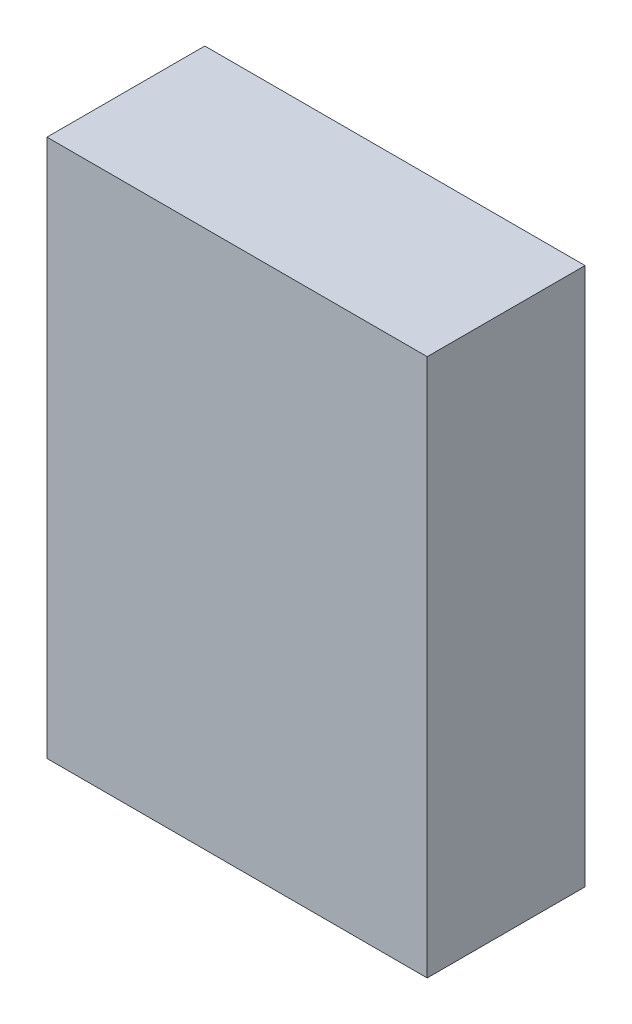
SolidWorks part; units mm, degrees
ref_plane "Front Plane" through (0, 0, 0) normal (0, 0, 1) x (1, 0, 0)
ref_plane "Top Plane" through (0, 0, 0) normal (0, 1, 0) x (1, 0, 0)
ref_plane "Right Plane" through (0, 0, 0) normal (1, 0, 0) x (0, 0, -1)
sketch "Sketch1" plane through (0, 0, 0) normal (0, 0, 1) x (1, 0, 0)
  line L1 (-26.5, -37.5) -> (26.5, -37.5)
  line L2 (-26.5, -37.5) -> (-26.5, 37.5)
  line L3 (-26.5, 37.5) -> (26.5, 37.5)
  line L4 (26.5, -37.5) -> (26.5, 37.5)
  line L5 (-26.5, -37.5) -> (26.5, 37.5) construction
  line L6 (-26.5, 37.5) -> (26.5, -37.5) construction
extrude "Envelope" add sketch "Sketch1" along normal blind 22
